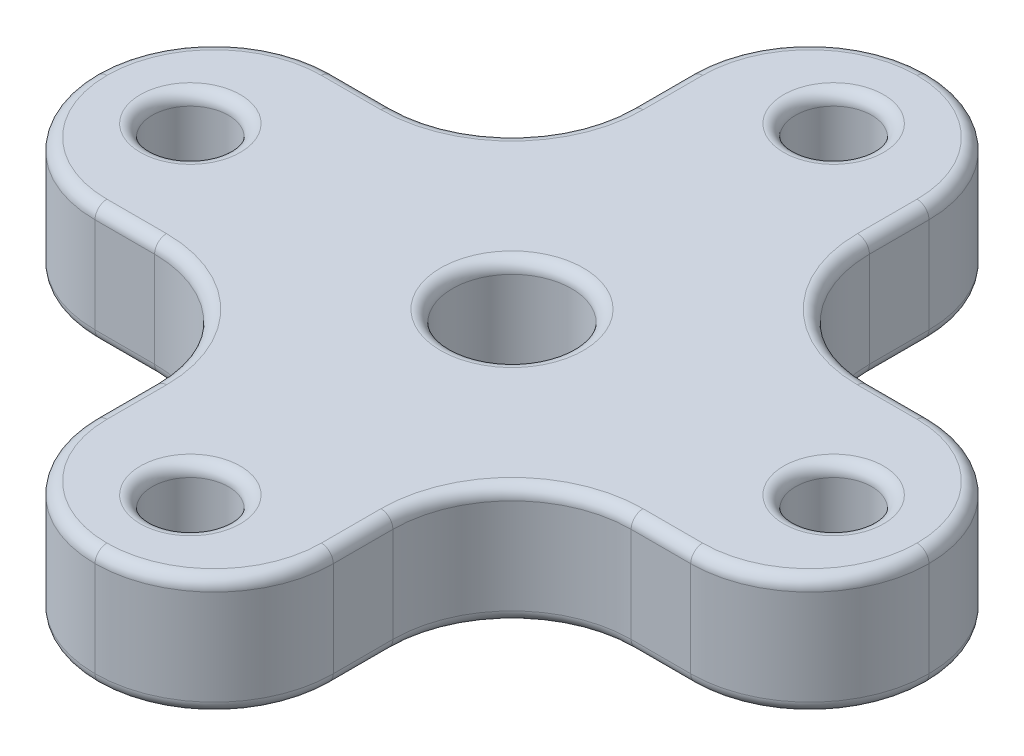
SolidWorks part; units mm, degrees
ref_plane "Front Plane" through (0, 0, 0) normal (0, 0, 1) x (1, 0, 0)
ref_plane "Top Plane" through (0, 0, 0) normal (0, 1, 0) x (1, 0, 0)
ref_plane "Right Plane" through (0, 0, 0) normal (1, 0, 0) x (0, 0, -1)
sketch "Sketch1" plane through (0, 0, 0) normal (0, 1, 0) x (1, 0, 0)
  line L1 (-17.5, -5) -> (17.5, -5)
  line L2 (-17.5, -5) -> (-17.5, 5)
  line L3 (-17.5, 5) -> (17.5, 5)
  line L4 (17.5, -5) -> (17.5, 5)
  line L5 (-17.5, -5) -> (17.5, 5) construction
  line L6 (-17.5, 5) -> (17.5, -5) construction
  line L7 (-5, -17.5) -> (5, -17.5)
  line L8 (-5, -17.5) -> (-5, 17.5)
  line L9 (-5, 17.5) -> (5, 17.5)
  line L10 (5, -17.5) -> (5, 17.5)
  line L11 (-5, -17.5) -> (5, 17.5) construction
  line L12 (-5, 17.5) -> (5, -17.5) construction
  circle A0 centre (0, 0) radius 2.5
  dimension "D1" = 5
  dimension "D2" = 35
  dimension "D3" = 10
  dimension "D4" = 35
  dimension "D5" = 10
extrude "Boss-Extrude1" add sketch "Sketch1" along normal blind 5 contours L10 L1 L4 L3 | L1 L10 L3 L8 A0 | L3 L10 L9 L8 | L1 L8 L3 L2 | L7 L10 L1 L8 region at (-11.25, 0, 0) region at (-4.8586, 0, 0) region at (0, 0, 11.25) region at (11.25, 0, 0) region at (0, 0, -11.25)
hole_wizard "M3 Clearance Hole1" positions "3DSketch1" profile "Sketch2" hole size "M3" standard "ANSI Metric" end condition through all
sketch3d "3DSketch1"
  line L0 (-17.5, 5, -5) -> (-5, 5, -5) construction
  line L1 (-17.5, 5, 5) -> (-17.5, 5, -5) construction
  line L2 (-5, 5, 17.5) -> (5, 5, 17.5) construction
  line L3 (5, 5, 17.5) -> (5, 5, 5) construction
  line L4 (17.5, 5, 5) -> (17.5, 5, -5) construction
  line L5 (5, 5, -5) -> (17.5, 5, -5) construction
  line L6 (-5, 5, -17.5) -> (5, 5, -17.5) construction
  line L7 (5, 5, -5) -> (5, 5, -17.5) construction
  point P0 (-13.5, 5, 0)
  point P2 (13.5, 5, 0)
  point P4 (0, 5, -13.5)
  point P6 (0, 5, 13.5)
  dimension "D1" = 5
  dimension "D2" = 4
  dimension "D3" = 4
  dimension "D4" = 5
  dimension "D5" = 4
  dimension "D6" = 5
  dimension "D7" = 4
  dimension "D8" = 5
sketch "Sketch2" plane through (-13.5, 5, 0) normal (1, 0, 0) x (0, 0, 1)
  line L0 (0, 0) -> (0, 5)
  line L1 (0, 5) -> (1.6, 5)
  line L2 (1.6, 5) -> (1.6, 0)
  line L5 (1.6, 0) -> (0, 0)
  line L11 (0, -6.35) -> (0, 107.95) construction
  dimension "Thru Hole Dia." = 3.2
  dimension "Thru Hole Depth" = 5
fillet "Fillet1" radius 5 12 edges at (-5, 2.5, -5) (5, 2.5, -5) (5, 2.5, 5) (-5, 2.5, 5) (5, 2.5, 17.5) (-5, 2.5, 17.5) (-17.5, 2.5, 5) (-17.5, 2.5, -5) (-5, 2.5, -17.5) (5, 2.5, -17.5) (17.5, 2.5, 5) (17.5, 2.5, -5)
fillet "Fillet2" radius 0.5 50 edges at (0, 0, 2.5) (6.4645, 0, 6.4645) (11.25, 0, 5) (16.0355, 0, 3.5355) (16.0355, 0, -3.5355) (11.25, 0, -5) (6.4645, 0, -6.4645) (5, 0, -11.25) (3.5355, 0, -16.0355) (-3.5355, 0, -16.0355) (-5, 0, -11.25) (-6.4645, 0, -6.4645) (-11.25, 0, -5) (-16.0355, 0, -3.5355) (-16.0355, 0, 3.5355) (-11.25, 0, 5) (-6.4645, 0, 6.4645) (-5, 0, 11.25) (-3.5355, 0, 16.0355) (3.5355, 0, 16.0355) (5, 0, 11.25) (0, 0, 15.1) (0, 0, -11.9) (13.5, 0, 1.6) (-13.5, 0, 1.6) (0, 5, 2.5) (-5, 5, 11.25) (-6.4645, 5, 6.4645) (-11.25, 5, 5) (-16.0355, 5, 3.5355) (-16.0355, 5, -3.5355) (-11.25, 5, -5) (-6.4645, 5, -6.4645) (-5, 5, -11.25) (-3.5355, 5, -16.0355) (3.5355, 5, -16.0355) (5, 5, -11.25) (6.4645, 5, -6.4645) (11.25, 5, -5) (16.0355, 5, -3.5355) (16.0355, 5, 3.5355) (11.25, 5, 5) (6.4645, 5, 6.4645) (5, 5, 11.25) (3.5355, 5, 16.0355) (-3.5355, 5, 16.0355) (0, 5, 15.1) (0, 5, -11.9) (13.5, 5, 1.6) (-13.5, 5, 1.6)
